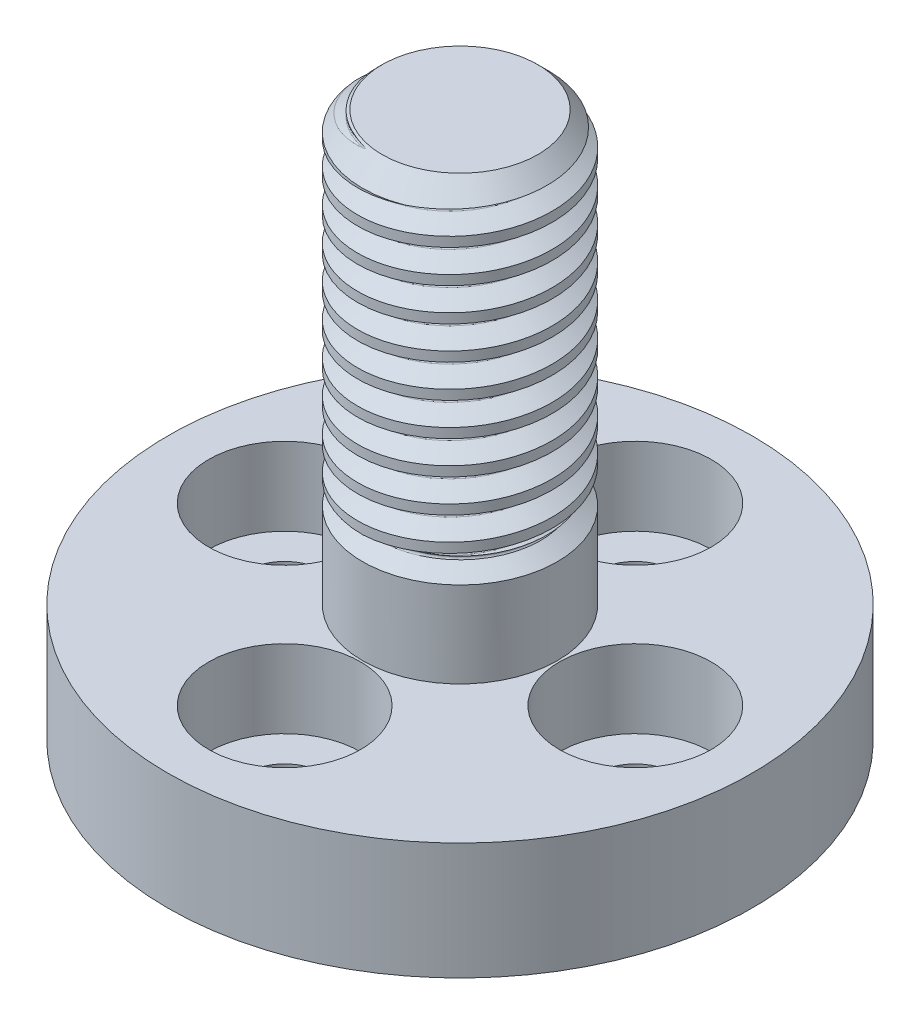
SolidWorks part; units mm, degrees
material "1060 Alloy"
ref_plane "Front Plane" through (0, 0, 0) normal (0, 0, 1) x (1, 0, 0)
ref_plane "Top Plane" through (0, 0, 0) normal (0, 1, 0) x (1, 0, 0)
ref_plane "Right Plane" through (0, 0, 0) normal (1, 0, 0) x (0, 0, -1)
sketch "Sketch1" plane through (0, 0, 0) normal (0, 1, 0) x (1, 0, 0)
  circle A0 centre (0, 0) radius 7.5
  dimension "D1" = 15
extrude "Boss-Extrude1" add sketch "Sketch1" along normal blind 3
sketch "Sketch2" plane through (0, 3, 0) normal (0, 1, 0) x (1, 0, 0)
  circle A0 centre (0, 0) radius 2.5
  dimension "D1" = 5
extrude "Boss-Extrude2" add sketch "Sketch2" along normal blind 11
ref_plane "Plane1" through (0, 5.5, 0) normal (0, -1, 0) x (-1, 0, 0)
sketch "Sketch3" plane through (0, 5.5, 0) normal (0, -1, 0) x (-1, 0, 0)
  circle A0 centre (0, 0) radius 2.5
  circle A1 centre (0, 0) radius 2.5
curve "Helix/Spiral1" pitch 0.85 height 8.925 turns 10.5
chamfer "Chamfer1" distance 0.5 angle 45 1 edges at (0, 14, 2.5)
sketch "Sketch4" plane through (0, 0, 0) normal (1, 0, 0) x (0, 0, -1)
  line L0 (-2.5, 3) -> (-2.5, 13.5)
  line L1 (2.5, 14) -> (2.5, 3)
  line L2 (-2.5, 5.2) -> (-2.5, 5.8)
  line L3 (-2.5, 3) -> (-2.5, 13.5) construction
  line L4 (-2.5, 5.8) -> (-2.0715, 5.5429)
  line L5 (-2.0715, 5.4571) -> (-2.5, 5.2)
  line L6 (0, 0) -> (0, 4.1643) construction
  arc A0 (-2.0715, 5.5429) -> (-2.0715, 5.4571) centre (-2.0972, 5.5) cw
  spline S0 degree 3 poles (997.1011, 31.8831) (129.9876, 3.6872) (-11.2729, 4.7036) (-1.8138, 5.6062) (-0.9816, 5.6594) (0, 5.7125) (0.9816, 5.7656) (1.8138, 5.8187) (2.3698, 5.8719) (2.5651, 5.925) (2.3698, 5.9781) (1.8138, 6.0312) (0.9816, 6.0844) (0, 6.1375) (-0.9816, 6.1906) (-1.8138, 6.2437) (-2.3698, 6.2969) (-2.5651, 6.35) (-2.3698, 6.4031) (-1.8138, 6.4562) (-0.9816, 6.5094) (0, 6.5625) (0.9816, 6.6156) (1.8138, 6.6687) (2.3698, 6.7219) (2.5651, 6.775) (2.3698, 6.8281) (1.8138, 6.8813) (0.9816, 6.9344) (0, 6.9875) (-0.9816, 7.0406) (-1.8138, 7.0937) (-2.3698, 7.1469) (-2.5651, 7.2) (-2.3698, 7.2531) (-1.8138, 7.3063) (-0.9816, 7.3594) (0, 7.4125) (0.9816, 7.4656) (1.8138, 7.5187) (2.3698, 7.5719) (2.5651, 7.625) (2.3698, 7.6781) (1.8138, 7.7313) (0.9816, 7.7844) (0, 7.8375) (-0.9816, 7.8906) (-1.8138, 7.9437) (-2.3698, 7.9969) (-2.5651, 8.05) (-2.3698, 8.1031) (-1.8138, 8.1562) (-0.9816, 8.2094) (0, 8.2625) (0.9816, 8.3156) (1.8138, 8.3687) (2.3698, 8.4219) (2.5651, 8.475) (2.3698, 8.5281) (1.8138, 8.5812) (0.9816, 8.6344) (0, 8.6875) (-0.9816, 8.7406) (-1.8138, 8.7937) (-2.3698, 8.8469) (-2.5651, 8.9) (-2.3698, 8.9531) (-1.8138, 9.0062) (-0.9816, 9.0594) (0, 9.1125) (0.9816, 9.1656) (1.8138, 9.2187) (2.3698, 9.2719) (2.5651, 9.325) (2.3698, 9.3781) (1.8138, 9.4312) (0.9816, 9.4844) (0, 9.5375) (-0.9816, 9.5906) (-1.8138, 9.6437) (-2.3698, 9.6969) (-2.5651, 9.75) (-2.3698, 9.8031) (-1.8138, 9.8562) (-0.9816, 9.9094) (0, 9.9625) (0.9816, 10.0156) (1.8138, 10.0687) (2.3698, 10.1219) (2.5651, 10.175) (2.3698, 10.2281) (1.8138, 10.2812) (0.9816, 10.3344) (0, 10.3875) (-0.9816, 10.4406) (-1.8138, 10.4937) (-2.3698, 10.5469) (-2.5651, 10.6) (-2.3698, 10.6531) (-1.8138, 10.7062) (-0.9816, 10.7594) (0, 10.8125) (0.9816, 10.8656) (1.8138, 10.9187) (2.3698, 10.9719) (2.5651, 11.025) (2.3698, 11.0781) (1.8138, 11.1312) (0.9816, 11.1844) (0, 11.2375) (-0.9816, 11.2906) (-1.8138, 11.3438) (-2.3698, 11.3969) (-2.5651, 11.45) (-2.3698, 11.5031) (-1.8138, 11.5563) (-0.9816, 11.6094) (0, 11.6625) (0.9816, 11.7156) (1.8138, 11.7688) (2.3698, 11.8219) (2.5651, 11.875) (2.3698, 11.9281) (1.8138, 11.9813) (0.9816, 12.0344) (0, 12.0875) (-0.9816, 12.1406) (-1.8138, 12.1937) (-2.3698, 12.2469) (-2.5651, 12.3) (-2.3698, 12.3531) (-1.8138, 12.4063) (-0.9816, 12.4594) (0, 12.5125) (0.9816, 12.5656) (1.8138, 12.6188) (2.3698, 12.6719) (2.5651, 12.725) (2.3698, 12.7781) (1.8138, 12.8313) (0.9816, 12.8844) (0, 12.9375) (-0.9816, 12.9906) (-1.8138, 13.0438) (-2.3698, 13.0969) (-2.5651, 13.15) (-2.3698, 13.2031) (-1.8138, 13.2563) (-0.9816, 13.3094) (0, 13.3625) (0.9816, 13.4156) (1.8138, 13.4688) (2.3698, 13.5219) (2.5651, 13.575) (2.3698, 13.6281) (1.8138, 13.6813) (0.9816, 13.7344) (0, 13.7875) (-0.9816, 13.8406) (-1.8138, 13.8938) (-2.3698, 13.9469) (-2.5651, 14) (-2.3698, 14.0531) (-1.8138, 14.1063) (-0.9816, 14.1594) (0, 14.2125) (0.9816, 14.2656) (1.8138, 14.3188) (11.2728, 15.2214) (-129.9862, 16.2378) (-997.0876, -11.9576) knots -0.285919 -0.285919 -0.285919 -0.285919 0.005952 0.011905 0.017857 0.02381 0.029762 0.035714 0.041667 0.047619 0.053571 0.059524 0.065476 0.071429 0.077381 0.083333 0.089286 0.095238 0.10119 0.107143 0.113095 0.119048 0.125 0.130952 0.136905 0.142857 0.14881 0.154762 0.160714 0.166667 0.172619 0.178571 0.184524 0.190476 0.196429 0.202381 0.208333 0.214286 0.220238 0.22619 0.232143 0.238095 0.244048 0.25 0.255952 0.261905 0.267857 0.27381 0.279762 0.285714 0.291667 0.297619 0.303571 0.309524 0.315476 0.321429 0.327381 0.333333 0.339286 0.345238 0.35119 0.357143 0.363095 0.369048 0.375 0.380952 0.386905 0.392857 0.39881 0.404762 0.410714 0.416667 0.422619 0.428571 0.434524 0.440476 0.446429 0.452381 0.458333 0.464286 0.470238 0.47619 0.482143 0.488095 0.494048 0.5 0.505952 0.511905 0.517857 0.52381 0.529762 0.535714 0.541667 0.547619 0.553571 0.559524 0.565476 0.571429 0.577381 0.583333 0.589286 0.595238 0.60119 0.607143 0.613095 0.619048 0.625 0.630952 0.636905 0.642857 0.64881 0.654762 0.660714 0.666667 0.672619 0.678571 0.684524 0.690476 0.696429 0.702381 0.708333 0.714286 0.720238 0.72619 0.732143 0.738095 0.744048 0.75 0.755952 0.761905 0.767857 0.77381 0.779762 0.785714 0.791667 0.797619 0.803571 0.809524 0.815476 0.821429 0.827381 0.833333 0.839286 0.845238 0.85119 0.857143 0.863095 0.869048 0.875 0.880952 0.886905 0.892857 0.89881 0.904762 0.910714 0.916667 0.922619 0.928571 0.934524 0.940476 0.946429 0.952381 0.958333 0.964286 0.970238 0.97619 0.982143 0.988095 0.994048 1.285918 1.285918 1.285918 1.285918 only from (-2.5, 5.5) to (2.5, 14.425) construction
  spline S1 degree 3 poles (-2.5, 5.5) (-2.5, 5.5176) (-2.3698, 5.5532) (-1.8138, 5.6062) (-0.9816, 5.6594) (0, 5.7125) (0.9816, 5.7656) (1.8138, 5.8187) (2.3698, 5.8719) (2.5651, 5.925) (2.3698, 5.9781) (1.8138, 6.0312) (0.9816, 6.0844) (0, 6.1375) (-0.9816, 6.1906) (-1.8138, 6.2437) (-2.3698, 6.2969) (-2.5651, 6.35) (-2.3698, 6.4031) (-1.8138, 6.4562) (-0.9816, 6.5094) (0, 6.5625) (0.9816, 6.6156) (1.8138, 6.6687) (2.3698, 6.7219) (2.5651, 6.775) (2.3698, 6.8281) (1.8138, 6.8813) (0.9816, 6.9344) (0, 6.9875) (-0.9816, 7.0406) (-1.8138, 7.0937) (-2.3698, 7.1469) (-2.5651, 7.2) (-2.3698, 7.2531) (-1.8138, 7.3063) (-0.9816, 7.3594) (0, 7.4125) (0.9816, 7.4656) (1.8138, 7.5187) (2.3698, 7.5719) (2.5651, 7.625) (2.3698, 7.6781) (1.8138, 7.7313) (0.9816, 7.7844) (0, 7.8375) (-0.9816, 7.8906) (-1.8138, 7.9437) (-2.3698, 7.9969) (-2.5651, 8.05) (-2.3698, 8.1031) (-1.8138, 8.1562) (-0.9816, 8.2094) (0, 8.2625) (0.9816, 8.3156) (1.8138, 8.3687) (2.3698, 8.4219) (2.5651, 8.475) (2.3698, 8.5281) (1.8138, 8.5812) (0.9816, 8.6344) (0, 8.6875) (-0.9816, 8.7406) (-1.8138, 8.7937) (-2.3698, 8.8469) (-2.5651, 8.9) (-2.3698, 8.9531) (-1.8138, 9.0062) (-0.9816, 9.0594) (0, 9.1125) (0.9816, 9.1656) (1.8138, 9.2187) (2.3698, 9.2719) (2.5651, 9.325) (2.3698, 9.3781) (1.8138, 9.4312) (0.9816, 9.4844) (0, 9.5375) (-0.9816, 9.5906) (-1.8138, 9.6437) (-2.3698, 9.6969) (-2.5651, 9.75) (-2.3698, 9.8031) (-1.8138, 9.8562) (-0.9816, 9.9094) (0, 9.9625) (0.9816, 10.0156) (1.8138, 10.0687) (2.3698, 10.1219) (2.5651, 10.175) (2.3698, 10.2281) (1.8138, 10.2812) (0.9816, 10.3344) (0, 10.3875) (-0.9816, 10.4406) (-1.8138, 10.4937) (-2.3698, 10.5469) (-2.5651, 10.6) (-2.3698, 10.6531) (-1.8138, 10.7062) (-0.9816, 10.7594) (0, 10.8125) (0.9816, 10.8656) (1.8138, 10.9187) (2.3698, 10.9719) (2.5651, 11.025) (2.3698, 11.0781) (1.8138, 11.1312) (0.9816, 11.1844) (0, 11.2375) (-0.9816, 11.2906) (-1.8138, 11.3438) (-2.3698, 11.3969) (-2.5651, 11.45) (-2.3698, 11.5031) (-1.8138, 11.5563) (-0.9816, 11.6094) (0, 11.6625) (0.9816, 11.7156) (1.8138, 11.7688) (2.3698, 11.8219) (2.5651, 11.875) (2.3698, 11.9281) (1.8138, 11.9813) (0.9816, 12.0344) (0, 12.0875) (-0.9816, 12.1406) (-1.8138, 12.1937) (-2.3698, 12.2469) (-2.5651, 12.3) (-2.3698, 12.3531) (-1.8138, 12.4063) (-0.9816, 12.4594) (0, 12.5125) (0.9816, 12.5656) (1.8138, 12.6188) (2.3698, 12.6719) (2.5651, 12.725) (2.3698, 12.7781) (1.8138, 12.8313) (0.9816, 12.8844) (0, 12.9375) (-0.9816, 12.9906) (-1.8138, 13.0438) (-2.3698, 13.0969) (-2.5651, 13.15) (-2.3698, 13.2031) (-1.8138, 13.2563) (-0.9816, 13.3094) (0, 13.3625) (0.9816, 13.4156) (1.8138, 13.4688) (2.3698, 13.5219) (2.5651, 13.575) (2.3698, 13.6281) (1.8138, 13.6813) (0.9816, 13.7344) (0, 13.7875) (-0.9816, 13.8406) (-1.8138, 13.8938) (-2.3698, 13.9469) (-2.5651, 14) (-2.3698, 14.0531) (-1.8138, 14.1063) (-0.9816, 14.1594) (0, 14.2125) (0.9816, 14.2656) (1.8138, 14.3188) (2.3698, 14.3718) (2.5, 14.4074) (2.5, 14.425) knots 0 0 0 0 0.005952 0.011905 0.017857 0.02381 0.029762 0.035714 0.041667 0.047619 0.053571 0.059524 0.065476 0.071429 0.077381 0.083333 0.089286 0.095238 0.10119 0.107143 0.113095 0.119048 0.125 0.130952 0.136905 0.142857 0.14881 0.154762 0.160714 0.166667 0.172619 0.178571 0.184524 0.190476 0.196429 0.202381 0.208333 0.214286 0.220238 0.22619 0.232143 0.238095 0.244048 0.25 0.255952 0.261905 0.267857 0.27381 0.279762 0.285714 0.291667 0.297619 0.303571 0.309524 0.315476 0.321429 0.327381 0.333333 0.339286 0.345238 0.35119 0.357143 0.363095 0.369048 0.375 0.380952 0.386905 0.392857 0.39881 0.404762 0.410714 0.416667 0.422619 0.428571 0.434524 0.440476 0.446429 0.452381 0.458333 0.464286 0.470238 0.47619 0.482143 0.488095 0.494048 0.5 0.505952 0.511905 0.517857 0.52381 0.529762 0.535714 0.541667 0.547619 0.553571 0.559524 0.565476 0.571429 0.577381 0.583333 0.589286 0.595238 0.60119 0.607143 0.613095 0.619048 0.625 0.630952 0.636905 0.642857 0.64881 0.654762 0.660714 0.666667 0.672619 0.678571 0.684524 0.690476 0.696429 0.702381 0.708333 0.714286 0.720238 0.72619 0.732143 0.738095 0.744048 0.75 0.755952 0.761905 0.767857 0.77381 0.779762 0.785714 0.791667 0.797619 0.803571 0.809524 0.815476 0.821429 0.827381 0.833333 0.839286 0.845238 0.85119 0.857143 0.863095 0.869048 0.875 0.880952 0.886905 0.892857 0.89881 0.904762 0.910714 0.916667 0.922619 0.928571 0.934524 0.940476 0.946429 0.952381 0.958333 0.964286 0.970238 0.97619 0.982143 0.988095 0.994048 1 1 1 1 construction
  point P11 (-2, 5.5)
  dimension "D3" = 0.05
  dimension "D1" = 0.6
  dimension "D2" = 0.5
sweep "Cut-Sweep1" cut profiles "Sketch4" path "Helix/Spiral1" align with end faces yes
sketch "Sketch5" plane through (0, 0, 0) normal (1, 0, 0) x (0, 0, -1)
  line L0 (0, 0) -> (0, 6.5967) construction
  line L3 (-2.5, 5.8) -> (-2.5, 5.2)
  line L4 (-2.0715, 5.5429) -> (-2.5, 5.8)
  line L5 (-2.5, 5.2) -> (-2.0715, 5.4571)
  line L6 (-2.5, 5.8) -> (-2.5, 5.2)
  line L7 (-2.0715, 5.5429) -> (-2.5, 5.8)
  line L8 (-2.5, 5.2) -> (-2.0715, 5.4571)
  arc A1 (-2.0715, 5.4571) -> (-2.0715, 5.5429) centre (-2.0972, 5.5) ccw
  arc A2 (-2.0715, 5.4571) -> (-2.0715, 5.5429) centre (-2.0972, 5.5) ccw
  dimension "D1" = 0
revolve "Cut-Revolve1" cut sketch "Sketch5" angle 360 about L0
sketch "Sketch7" plane through (0, 0, 0) normal (0, -1, 0) x (1, 0, 0)
  line L0 (0, 0) -> (4.5, 0) construction
  circle A0 centre (0, 0) radius 4.5 construction
  circle A1 centre (4.5, 0) radius 1
  dimension "D1" = 9
  dimension "D2" = 2
extrude "Cut-Extrude1" cut sketch "Sketch7" against normal blind 11
sketch "Sketch8" plane through (0, 3, 0) normal (0, 1, 0) x (1, 0, 0)
  circle A0 centre (4.5, 0) radius 1 construction
  circle A1 centre (4.5, 0) radius 1 construction
  circle A2 centre (4.5, 0) radius 1.95
  dimension "D1" = 3.9
extrude "Cut-Extrude2" cut sketch "Sketch8" against normal blind 2
pattern_circular "CirPattern1" count 4 over 360 about axis through (0, 0, 0) along (0, 1, 0) of "Cut-Extrude1", "Cut-Extrude2"
sketch "Sketch9" plane through (0, 0, 0) normal (0, -1, 0) x (1, 0, 0)
  circle A0 centre (0, 0) radius 1
  dimension "D1" = 2
extrude "Cut-Extrude3" cut sketch "Sketch9" against normal blind 5
